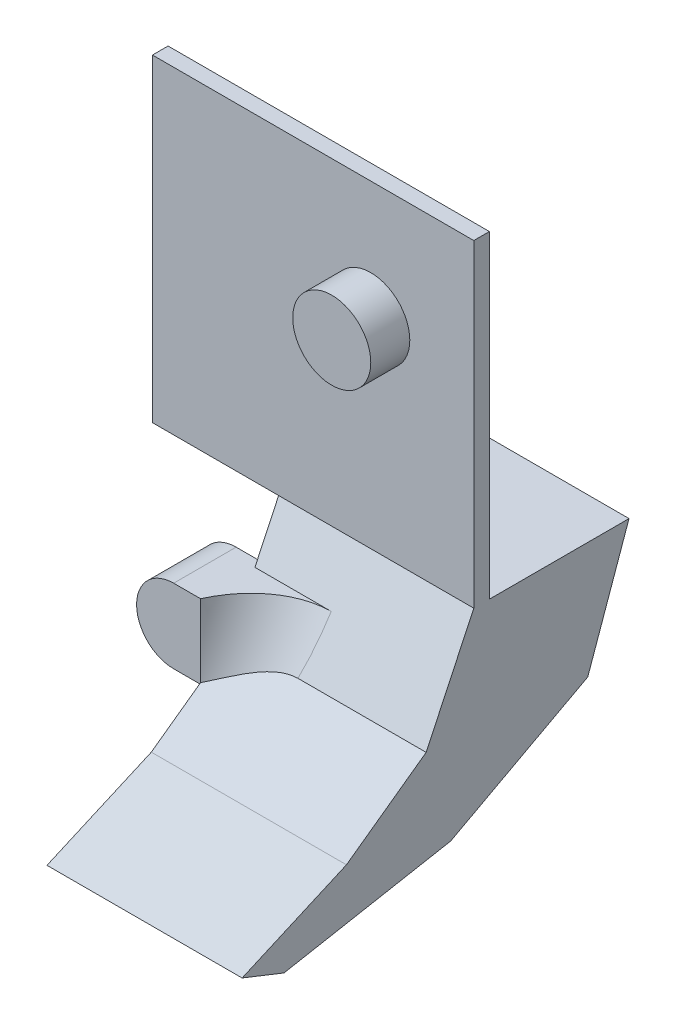
SolidWorks part; units mm, degrees
ref_plane "Front Plane" through (0, 0, 0) normal (0, 0, 1) x (1, 0, 0)
ref_plane "Top Plane" through (0, 0, 0) normal (0, 1, 0) x (1, 0, 0)
ref_plane "Right Plane" through (0, 0, 0) normal (1, 0, 0) x (0, 0, -1)
sketch "Sketch1" plane through (0, 0, 0) normal (1, 0, 0) x (0, 0, -1)
  line L8 (-29.6788, -26.1888) -> (-24.3121, -28.3127)
  line L9 (-24.3121, -28.3127) -> (-2.9567, -24.355)
  line L10 (-2.9567, -24.355) -> (14.5987, -14.9352)
  line L11 (14.5987, -14.9352) -> (19.8883, 0)
  line L12 (19.8883, 0) -> (0, 0)
  line L13 (0, 0) -> (-6.1009, -12.9442)
  line L14 (-6.1009, -12.9442) -> (-16.3122, -20.3129)
  line L15 (-16.3122, -20.3129) -> (-29.6788, -26.1888)
  point P0 (-24.3121, -28.3127)
extrude "Boss-Extrude1" add sketch "Sketch1" along normal mid plane 25
sketch "Sketch2" plane through (0, 0, 0) normal (0, 0, 1) x (1, 0, 0)
  line L1 (12.5, 0) -> (-28.6635, 0)
  line L2 (12.5, 0) -> (12.5, 40.7911)
  line L3 (12.5, 40.7911) -> (-28.6635, 40.7911)
  line L4 (-28.6635, 0) -> (-28.6635, 40.7911)
extrude "Boss-Extrude2" add sketch "Sketch2" against normal blind 2
ref_plane "Plane1" through (0, 0, 10) normal (0, 0, 1) x (1, 0, 0)
sketch "Sketch3" plane through (0, 0, 10) normal (0, 0, 1) x (1, 0, 0)
  line L0 (-12.5, -24.355) -> (-12.5, -14.9352) construction
  line L1 (-15.9469, -6.449) -> (-12.5, -6.449)
  line L3 (-15.9469, -15.949) -> (-12.5, -15.949)
  line L4 (-12.5, -6.449) -> (-12.5, -15.949)
  arc A0 (-15.9469, -6.449) -> (-15.9469, -15.949) centre (-15.9469, -11.199) ccw
extrude "Boss-Extrude3" add sketch "Sketch3" against normal blind 8
fillet "Fillet1" radius 10 1 edges at (-12.5, -9.6966, 4.5702)
sketch "Sketch4" plane through (0, 0, 0) normal (0, 0, 1) x (1, 0, 0)
  circle A0 centre (-0.6969, 25.6345) radius 5
extrude "Boss-Extrude4" add sketch "Sketch4" along normal blind 5
